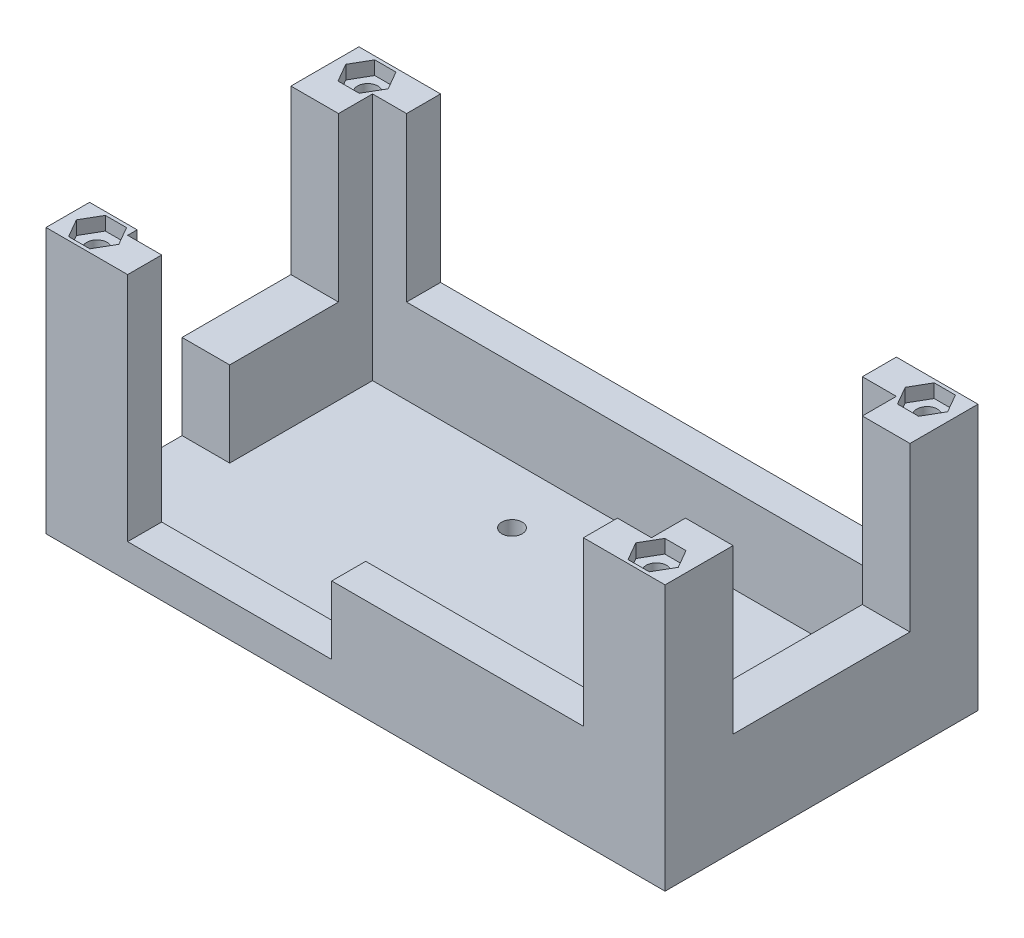
SolidWorks part; units mm, degrees
ref_plane "Front Plane" through (0, 0, 0) normal (0, 0, 1) x (1, 0, 0)
ref_plane "Top Plane" through (0, 0, 0) normal (0, 1, 0) x (1, 0, 0)
ref_plane "Right Plane" through (0, 0, 0) normal (1, 0, 0) x (0, 0, -1)
sketch "Sketch1" plane through (0, 0, 0) normal (0, 1, 0) x (1, 0, 0)
  line L0 (38.5, 36) -> (38.5, 0) construction
  line L1 (0, 0) -> (77, 0)
  line L2 (0, 0) -> (0, 36)
  line L3 (0, 36) -> (77, 36)
  line L4 (77, 0) -> (77, 36)
  line L5 (0, 18) -> (77, 18) construction
  line L6 (-4.1765, 0.9) -> (-1.0588, 0.9)
  line L7 (-7, 31) -> (-7, 41)
  line L8 (-7, 31) -> (0, 31)
  line L9 (0, 31) -> (0, 36)
  line L10 (-7, 41) -> (5, 41)
  line L11 (5, 41) -> (5, 36)
  line L12 (0, 31) -> (0, 36)
  line L13 (5, -5) -> (5, 0)
  line L14 (-7, -5) -> (5, -5)
  line L15 (-7, 5) -> (-7, -5)
  line L16 (-7, 5) -> (0, 5)
  line L17 (72, -5) -> (72, 0)
  line L18 (84, -5) -> (72, -5)
  line L19 (84, 5) -> (84, -5)
  line L20 (84, 5) -> (77, 5)
  line L21 (84, 31) -> (77, 31)
  line L22 (84, 31) -> (84, 41)
  line L23 (72, 41) -> (72, 36)
  line L24 (84, 41) -> (72, 41)
  line L29 (0, 5) -> (0, 0)
  line L30 (72, 0) -> (77, 0)
  line L31 (72, 36) -> (77, 36)
  line L35 (5, 36) -> (72, 36)
  line L36 (0, 31) -> (0, 36)
  line L37 (5, 41) -> (72, 41)
  line L38 (84, 31) -> (84, 5)
  line L39 (0, 5) -> (0, 0)
  line L40 (5, -5) -> (72, -5)
  line L41 (-7, 31) -> (-7, 5)
  line L66 (-5.7354, -1.8) -> (-4.1765, 0.9)
  line L73 (-1.0588, 35.1) -> (0.5, 37.8)
  line L74 (0.5, 37.8) -> (-1.0588, 40.5)
  line L75 (-1.0588, 40.5) -> (-4.1765, 40.5)
  line L76 (-4.1765, 40.5) -> (-5.7354, 37.8)
  line L77 (-5.7354, 37.8) -> (-4.1765, 35.1)
  line L78 (-4.1765, 35.1) -> (-1.0588, 35.1)
  line L79 (-4.1765, -4.5) -> (-5.7354, -1.8)
  line L80 (-1.0588, -4.5) -> (-4.1765, -4.5)
  line L81 (0.5, -1.8) -> (-1.0588, -4.5)
  line L82 (-1.0588, 0.9) -> (0.5, -1.8)
  line L83 (82.7354, -1.8) -> (81.1765, 0.9)
  line L84 (81.1765, -4.5) -> (82.7354, -1.8)
  line L85 (78.0588, -4.5) -> (81.1765, -4.5)
  line L86 (76.5, -1.8) -> (78.0588, -4.5)
  line L87 (78.0588, 0.9) -> (76.5, -1.8)
  line L88 (81.1765, 0.9) -> (78.0588, 0.9)
  line L89 (81.1765, 35.1) -> (78.0588, 35.1)
  line L90 (82.7354, 37.8) -> (81.1765, 35.1)
  line L91 (81.1765, 40.5) -> (82.7354, 37.8)
  line L92 (78.0588, 40.5) -> (81.1765, 40.5)
  line L93 (76.5, 37.8) -> (78.0588, 40.5)
  line L94 (78.0588, 35.1) -> (76.5, 37.8)
  line L96 (29, 8.5) -> (48, 8.5) construction
  line L97 (29, 8.5) -> (29, 27.5) construction
  line L98 (29, 27.5) -> (48, 27.5) construction
  line L99 (48, 8.5) -> (48, 27.5) construction
  line L100 (29, 8.5) -> (48, 27.5) construction
  line L101 (29, 27.5) -> (48, 8.5) construction
  circle A0 centre (-2.6177, 37.8) radius 2.5 construction
  circle A5 centre (-2.6177, 37.9) radius 1.5
  circle A6 centre (-2.6177, -1.9) radius 1.5
  circle A7 centre (79.6177, -1.9) radius 1.5
  circle A8 centre (79.6177, 37.9) radius 1.5
  circle A9 centre (29, 8.5) radius 1.5
  circle A10 centre (29, 27.5) radius 1.5
  circle A11 centre (48, 27.5) radius 1.5
  circle A12 centre (48, 8.5) radius 1.5
  point P5 (0, 18)
  point P13 (0, 31)
  point P64 (38.5, 18)
  dimension "D12" = 19
  dimension "D10" = 5
  dimension "D11" = 3
  dimension "D14" = 3
  dimension "D15" = 3
  dimension "D16" = 3
  dimension "D17" = 3
  dimension "D1" = 77
  dimension "D2" = 36
  dimension "D3" = 5
  dimension "D4" = 5
  dimension "D5" = 7
  dimension "D6" = 5
  dimension "D7" = 5.4
  dimension "D8" = 0.5
  dimension "D9" = 0.5
  dimension "D13" = 19
extrude "Boss-Extrude7" add sketch "Sketch1" along normal blind 39 contours L16 L15 L14 L13 L1 L2 L89 L94 L93 L92 L91 L90 | L19 L20 L4 L1 L17 L18 L85 L87 | L11 L10 L7 L8 L2 L3 | L22 L24 L23 L3 L4 L21 L81 region at (2.5, 0, 0.1562) region at (74.5, 0, 0.1562) region at (-3.5, 0, -31.1562) region at (77.1562, 0, -33.5)
extrude "Boss-Extrude8" add sketch "Sketch1<11>" along normal blind 2.5 contours L1 L4 L3 L2 region at (38.5, 0, -18)
sketch "Sketch1<11>" plane through (0, 0, 0) normal (0, 1, 0) x (1, 0, 0) same geometry as "Sketch1"
extrude "Boss-Extrude9" add sketch "Sketch1<12>" along normal blind 15 contours L13 L40 L17 L1 | L8 L41 L16 L2 | L37 L11 L3 L23 | L38 L21 L4 L20 region at (38.5, 0, 2.5) region at (-3.5, 0, -18) region at (80.5, 0, -18) region at (38.5, 0, -38.5)
sketch "Sketch1<12>" plane through (0, 0, 0) normal (0, 1, 0) x (1, 0, 0) same geometry as "Sketch1"
extrude "Boss-Extrude12" add sketch "Sketch1<19>" along normal blind 37 contours L77 L78 L73 L74 L75 L76 A5 | L82 L6 L66 L79 L80 L81 A6 | L83 L88 L87 L86 L85 L84 A7 | L94 L89 L90 L91 L92 L93 A8 region at (-2.6177, 0, -0.8175) region at (-2.6177, 0, -35.1825) region at (81.8845, 0, 3.1088) region at (79.6177, 0, -35.1825)
sketch "Sketch1<19>" plane through (0, 0, 0) normal (0, 1, 0) x (1, 0, 0) same geometry as "Sketch1"
extrude "Boss-Extrude13" add sketch "Sketch1<20>" along normal blind 15 contours A5 | A6 | A7 | A8 region at (-2.6177, 0, -37.9) region at (-2.6177, 0, 1.9) region at (79.6177, 0, 1.9) region at (79.6177, 0, -37.9)
sketch "Sketch1<20>" plane through (0, 0, 0) normal (0, 1, 0) x (1, 0, 0) same geometry as "Sketch1"
sketch "Sketch4" plane through (0, 0, 0) normal (1, 0, 0) x (0, 0, -1)
  line L0 (0, 39) -> (5, 39) construction
  line L1 (1.4, 39) -> (15, 39)
  line L2 (1.4, 39) -> (1.4, 2.5)
  line L3 (1.4, 2.5) -> (15, 2.5)
  line L4 (15, 39) -> (15, 2.5)
  line L5 (0, 2.5) -> (36, 2.5) construction
  line L6 (5, 39) -> (5, 15) construction
  dimension "D1" = 0.5
  dimension "D2" = 10
extrude "Cut-Extrude2" cut sketch "Sketch4" against normal through all
sketch "Sketch5" plane through (0, 0, 5) normal (0, 0, 1) x (1, 0, 0)
  line L0 (5, 15) -> (72, 15) construction
  line L6 (5, 15) -> (35, 15)
  line L7 (5, 15) -> (5, 5)
  line L8 (5, 5) -> (35, 5)
  line L9 (35, 15) -> (35, 5)
  point P0 (38.5, 15)
  point P6 (38.5, 15)
  point P7 (38.5327, 15)
  dimension "D1" = 30
  dimension "D2" = 10
extrude "Cut-Extrude4" cut sketch "Sketch5" against normal blind 15
